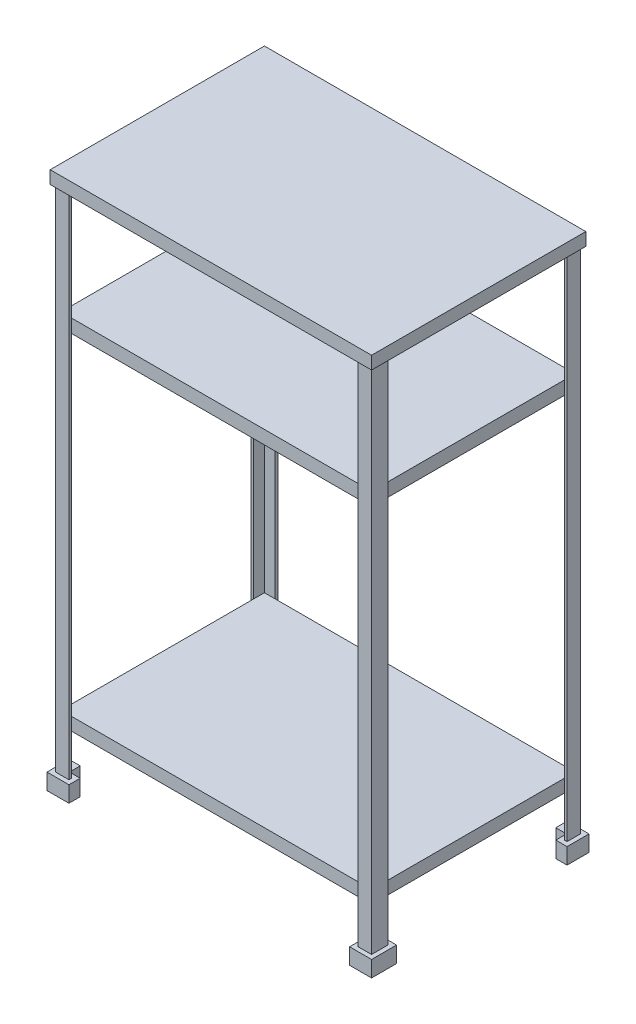
SolidWorks part; units mm, degrees
ref_plane "Alzado" through (0, 0, 0) normal (0, 0, 1) x (1, 0, 0)
ref_plane "Planta" through (0, 0, 0) normal (0, 1, 0) x (1, 0, 0)
ref_plane "Vista lateral" through (0, 0, 0) normal (1, 0, 0) x (0, 0, -1)
sketch "Croquis1" plane through (0, 0, 0) normal (0, 1, 0) x (1, 0, 0)
  line L1 (300, -200) -> (-300, -200)
  line L2 (300, -200) -> (300, 200)
  line L3 (300, 200) -> (-300, 200)
  line L4 (-300, -200) -> (-300, 200)
  line L5 (300, -200) -> (-300, 200) construction
  line L6 (300, 200) -> (-300, -200) construction
  point P0 (0, 0)
  dimension "D1" = 400
  dimension "D2" = 600
extrude "Saliente-Extruir1" add sketch "Croquis1" along normal blind 4
sketch "Croquis2" plane through (0, 0, 0) normal (0, -1, 0) x (1, 0, 0)
  line L0 (-295, 195) -> (-295, -195)
  line L1 (-295, -195) -> (295, -195)
  line L2 (295, -195) -> (295, 195)
  line L3 (295, 195) -> (-295, 195)
  line L4 (-300, 200) -> (-300, -200)
  line L5 (-300, -200) -> (300, -200)
  line L6 (300, -200) -> (300, 200)
  line L7 (300, 200) -> (-300, 200)
  line L8 (-300, 200) -> (-300, -200)
  line L9 (-300, -200) -> (300, -200)
  line L10 (300, -200) -> (300, 200)
  line L11 (300, 200) -> (-300, 200)
  dimension "D1" = 0
  dimension "D2" = 5
extrude "Saliente-Extruir2" add sketch "Croquis2" along normal blind 20
sketch "Croquis3" plane through (0, 0, 0) normal (0, -1, 0) x (1, 0, 0)
  line L0 (-270, 190) -> (-290, 190)
  line L1 (-295, 195) -> (-270, 195)
  line L2 (-295, 195) -> (-295, 170)
  line L3 (-295, 170) -> (-290, 170)
  line L4 (-270, 195) -> (-270, 190)
  line L5 (-290, 190) -> (-290, 170)
  line L6 (270, 195) -> (295, 195)
  line L7 (295, 195) -> (-295, 195) construction
  line L8 (295, 195) -> (295, 164.3409)
  line L9 (295, -195) -> (295, 195) construction
  line L10 (270, -195) -> (295, -195)
  line L11 (-295, -195) -> (295, -195) construction
  line L12 (295, -195) -> (295, -170)
  line L13 (295, -195) -> (295, 195) construction
  line L14 (-295, -170) -> (-295, -195)
  line L15 (-295, 195) -> (-295, -195) construction
  line L16 (-295, -195) -> (-270, -195)
  line L17 (-295, -195) -> (295, -195) construction
  line L18 (270, 195) -> (270, 190)
  line L19 (270, 190) -> (290, 190)
  line L20 (290, 190) -> (290, 164.3409)
  line L21 (290, 164.3409) -> (295, 164.3409)
  line L22 (-295, -170) -> (-290, -170)
  line L23 (-290, -170) -> (-290, -190)
  line L24 (-290, -190) -> (-270, -190)
  line L25 (-270, -190) -> (-270, -195)
  line L26 (295, -170) -> (290, -170)
  line L27 (290, -170) -> (290, -190)
  line L28 (290, -190) -> (270, -190)
  line L29 (270, -190) -> (270, -195)
  dimension "D1" = 5
  dimension "D2" = 5
  dimension "D3" = 25
  dimension "D4" = 25
  dimension "D5" = 25
  dimension "D6" = 25
  dimension "D7" = 25
  dimension "D8" = 30.6591
  dimension "D9" = 5
  dimension "D10" = 5
  dimension "D11" = 5
  dimension "D12" = 5
  dimension "D13" = 25
  dimension "D14" = 25
  dimension "D15" = 5
  dimension "D16" = 5
extrude "Saliente-Extruir3" add sketch "Croquis3" along normal blind 1000
sketch "Croquis4" plane through (0, -1000, 0) normal (0, -1, 0) x (1, 0, 0)
  line L0 (-303, 203) -> (-303, 162)
  line L1 (-303, 162) -> (-282, 162)
  line L2 (-282, 162) -> (-282, 182)
  line L3 (-282, 182) -> (-262, 182)
  line L4 (-262, 182) -> (-262, 203)
  line L5 (-262, 203) -> (-303, 203)
  line L6 (-295, 195) -> (-295, 170)
  line L7 (-295, 170) -> (-290, 170)
  line L8 (-290, 170) -> (-290, 190)
  line L9 (-290, 190) -> (-270, 190)
  line L10 (-270, 190) -> (-270, 195)
  line L11 (-270, 195) -> (-295, 195)
  line L12 (-295, 195) -> (-295, 170)
  line L13 (-295, 170) -> (-290, 170)
  line L14 (-290, 170) -> (-290, 190)
  line L15 (-290, 190) -> (-270, 190)
  line L16 (-270, 190) -> (-270, 195)
  line L17 (-270, 195) -> (-295, 195)
  line L18 (-282, -162) -> (-303, -162)
  line L19 (-303, -162) -> (-303, -203)
  line L20 (-303, -203) -> (-262, -203)
  line L21 (-262, -203) -> (-262, -182)
  line L22 (-262, -182) -> (-282, -182)
  line L23 (-282, -182) -> (-282, -162)
  line L24 (-290, -170) -> (-295, -170)
  line L25 (-295, -170) -> (-295, -195)
  line L26 (-295, -195) -> (-270, -195)
  line L27 (-270, -195) -> (-270, -190)
  line L28 (-270, -190) -> (-290, -190)
  line L29 (-290, -190) -> (-290, -170)
  line L30 (-290, -170) -> (-295, -170)
  line L31 (-295, -170) -> (-295, -195)
  line L32 (-295, -195) -> (-270, -195)
  line L33 (-270, -195) -> (-270, -190)
  line L34 (-270, -190) -> (-290, -190)
  line L35 (-290, -190) -> (-290, -170)
  line L36 (262, 203) -> (262, 182)
  line L37 (262, 182) -> (282, 182)
  line L38 (282, 182) -> (282, 156.3409)
  line L39 (282, 156.3409) -> (303, 156.3409)
  line L40 (303, 156.3409) -> (303, 203)
  line L41 (303, 203) -> (262, 203)
  line L42 (270, 195) -> (270, 190)
  line L43 (270, 190) -> (290, 190)
  line L44 (290, 190) -> (290, 164.3409)
  line L45 (290, 164.3409) -> (295, 164.3409)
  line L46 (295, 164.3409) -> (295, 195)
  line L47 (295, 195) -> (270, 195)
  line L48 (270, 195) -> (270, 190)
  line L49 (270, 190) -> (290, 190)
  line L50 (290, 190) -> (290, 164.3409)
  line L51 (290, 164.3409) -> (295, 164.3409)
  line L52 (295, 164.3409) -> (295, 195)
  line L53 (295, 195) -> (270, 195)
  line L54 (262, -182) -> (262, -203)
  line L55 (262, -203) -> (303, -203)
  line L56 (303, -203) -> (303, -162)
  line L57 (303, -162) -> (282, -162)
  line L58 (282, -162) -> (282, -182)
  line L59 (282, -182) -> (262, -182)
  line L60 (270, -190) -> (270, -195)
  line L61 (270, -195) -> (295, -195)
  line L62 (295, -195) -> (295, -170)
  line L63 (295, -170) -> (290, -170)
  line L64 (290, -170) -> (290, -190)
  line L65 (290, -190) -> (270, -190)
  line L66 (270, -190) -> (270, -195)
  line L67 (270, -195) -> (295, -195)
  line L68 (295, -195) -> (295, -170)
  line L69 (295, -170) -> (290, -170)
  line L70 (290, -170) -> (290, -190)
  line L71 (290, -190) -> (270, -190)
  dimension "D1" = 0
  dimension "D2" = 8
  dimension "D3" = 0
  dimension "D4" = 8
  dimension "D5" = 0
  dimension "D6" = 8
  dimension "D7" = 0
  dimension "D8" = 8
extrude "Saliente-Extruir4" add sketch "Croquis4" against normal blind 30
sketch "Croquis5" plane through (0, 0, -190) normal (0, 0, 1) x (1, 0, 0)
  line L0 (-290, -970) -> (-290, 0) construction
  line L5 (-300, 4) -> (300, 4) construction
  line L6 (-290, -226) -> (290, -226)
  line L7 (-290, -226) -> (-290, -251)
  line L8 (-290, -251) -> (290, -251)
  line L9 (290, -970) -> (290, 0) construction
  line L10 (-290, -870) -> (290, -870)
  line L11 (-290, -870) -> (-290, -894)
  line L12 (-290, -894) -> (290, -894)
  line L13 (290, -870) -> (290, -894)
  line L14 (300, -20) -> (-300, -20) construction
  line L15 (290, -226) -> (290, -251)
  point P8 (0, 0)
  point P9 (0, 0)
  dimension "D1" = 850
  dimension "D2" = 25
  dimension "D3" = 24
  dimension "D4" = 230
extrude "Saliente-Extruir5" add sketch "Croquis5" along direction (0, 0, 1) on the side of the normal up to surface (380 mm away) up to face at (-280, -485, 190)
sketch "Croquis7" plane through (0, -894, 0) normal (0, -1, 0) x (1, 0, 0)
  line L24 (-270, 185) -> (-285, 185)
  line L25 (-285, 185) -> (-285, 170)
  line L26 (-285, 170) -> (-285, -170)
  line L27 (-285, -170) -> (-285, -185)
  line L28 (-285, -185) -> (-270, -185)
  line L29 (-270, -185) -> (270, -185)
  line L30 (270, -185) -> (285, -185)
  line L31 (285, -185) -> (285, -170)
  line L32 (285, -170) -> (285, 164.3409)
  line L33 (285, 164.3409) -> (285, 185)
  line L34 (285, 185) -> (270, 185)
  line L35 (270, 185) -> (-270, 185)
  line L36 (-270, 185) -> (-285, 185)
  line L37 (-285, 185) -> (-285, 170)
  line L38 (-285, 170) -> (-285, -170)
  line L39 (-285, -170) -> (-285, -185)
  line L40 (-285, -185) -> (-270, -185)
  line L41 (-270, -185) -> (270, -185)
  line L42 (270, -185) -> (285, -185)
  line L43 (285, -185) -> (285, -170)
  line L44 (285, -170) -> (285, 164.3409)
  line L45 (285, 164.3409) -> (285, 185)
  line L46 (285, 185) -> (270, 185)
  line L47 (270, 185) -> (-270, 185)
  dimension "D1" = 5
extrude "Cortar-Extruir2" cut sketch "Croquis7" against normal blind 18
